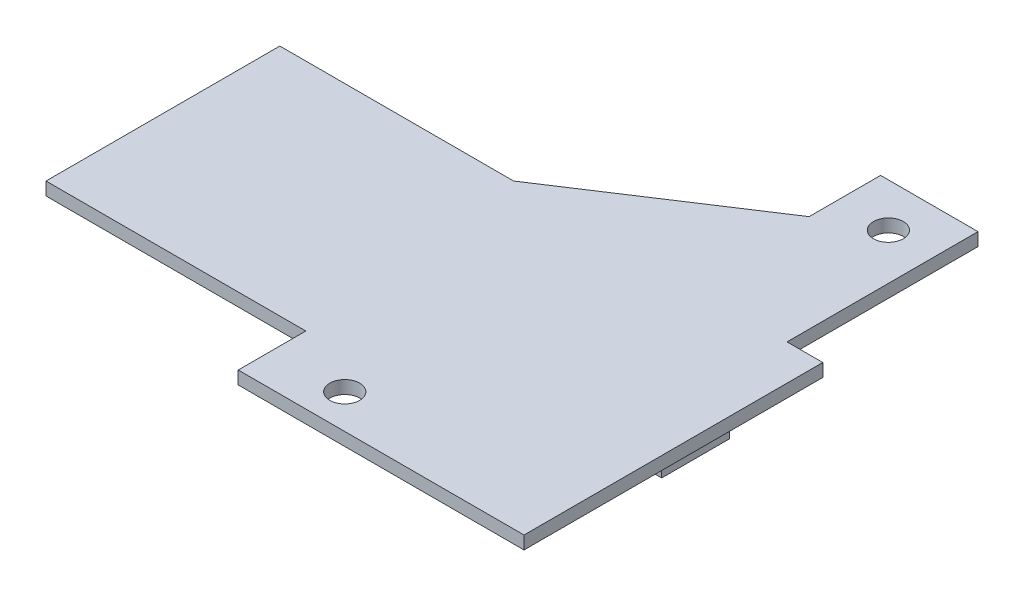
SolidWorks part; units mm, degrees
ref_plane "Спереди" through (0, 0, 0) normal (0, 0, 1) x (1, 0, 0)
ref_plane "Сверху" through (0, 0, 0) normal (0, 1, 0) x (1, 0, 0)
ref_plane "Справа" through (0, 0, 0) normal (1, 0, 0) x (0, 0, -1)
sketch "Эскиз1" plane through (0, 0, 0) normal (0, 1, 0) x (1, 0, 0)
  line L0 (0, 0) -> (-24058.8431, 0) construction
  line L1 (0, 0) -> (0, 24058.8431) construction
  line L13 (0, 0) -> (0, 18)
  line L14 (0, 18) -> (18, 18)
  line L15 (18, 18) -> (31.75, 27)
  line L16 (31.75, 27) -> (31.75, 32.5)
  line L17 (31.75, 32.5) -> (39.25, 32.5)
  line L18 (39.25, 32.5) -> (39.25, 17.8)
  line L19 (39.25, 17.8) -> (42, 17.8)
  line L20 (42, 17.8) -> (42, -5.2)
  line L21 (42, -5.2) -> (20, -5.2)
  line L22 (20, -5.2) -> (20, 0)
  line L23 (20, 0) -> (0, 0)
  point P13 (36.4271, 17.9269)
  dimension "D1" = 18
  dimension "D2" = 18
  dimension "D3" = 42
  dimension "D4" = 7.5
  dimension "D5" = 5.5
  dimension "D6" = 14.7
  dimension "D7" = 2.75
  dimension "D8" = 23
  dimension "D9" = 14.5
  dimension "D10" = 22
  dimension "D11" = 37.7
extrude "Бобышка-Вытянуть1" add sketch "Эскиз1" along normal blind 1
sketch "Эскиз2" plane through (0, 1, 0) normal (0, 1, 0) x (1, 0, 0)
  line L0 (39.25, 17.8) -> (39.25, 32.5) construction
  line L2 (31.75, 32.5) -> (31.75, 27) construction
  line L5 (39.25, 32.5) -> (31.75, 32.5) construction
  circle A0 centre (35.7, 29.15) radius 1.15
  dimension "D1" = 2.3
  dimension "D3" = 2.8
  dimension "D4" = 2.2
  dimension "D2" = 2.4
extrude "Вырез-Вытянуть1" cut sketch "Эскиз2" against normal through all
sketch "Эскиз3" plane through (0, 1, 0) normal (0, 1, 0) x (1, 0, 0)
  line L1 (20, -5.2) -> (42, -5.2) construction
  line L6 (20, 0) -> (20, -5.2) construction
  line L10 (42, -5.2) -> (42, 17.8) construction
  circle A0 centre (25.55, -2.55) radius 1.15
  dimension "D1" = 2.3
  dimension "D2" = 1.5
  dimension "D3" = 4.4
  dimension "D4" = 15.3
extrude "Вырез-Вытянуть2" cut sketch "Эскиз3" against normal through all
sketch "Эскиз4" plane through (0, 0, 0) normal (0, -1, 0) x (1, 0, 0)
  line L0 (0, -18) -> (0, 0) construction
  line L1 (41, -11.6) -> (35.8, -11.6)
  line L2 (41, -11.6) -> (41, -6.4)
  line L3 (41, -6.4) -> (35.8, -6.4)
  line L4 (35.8, -11.6) -> (35.8, -6.4)
  line L5 (41, -11.6) -> (35.8, -6.4) construction
  line L6 (41, -6.4) -> (35.8, -11.6) construction
  line L7 (20, 5.2) -> (42, 5.2) construction
  point P0 (38.4, -9)
  point P5 (36.0239, -6.4733)
  dimension "D1" = 5.2
  dimension "D2" = 41
  dimension "D3" = 16.8
extrude "Бобышка-Вытянуть2" add sketch "Эскиз4" along normal blind 1.5
